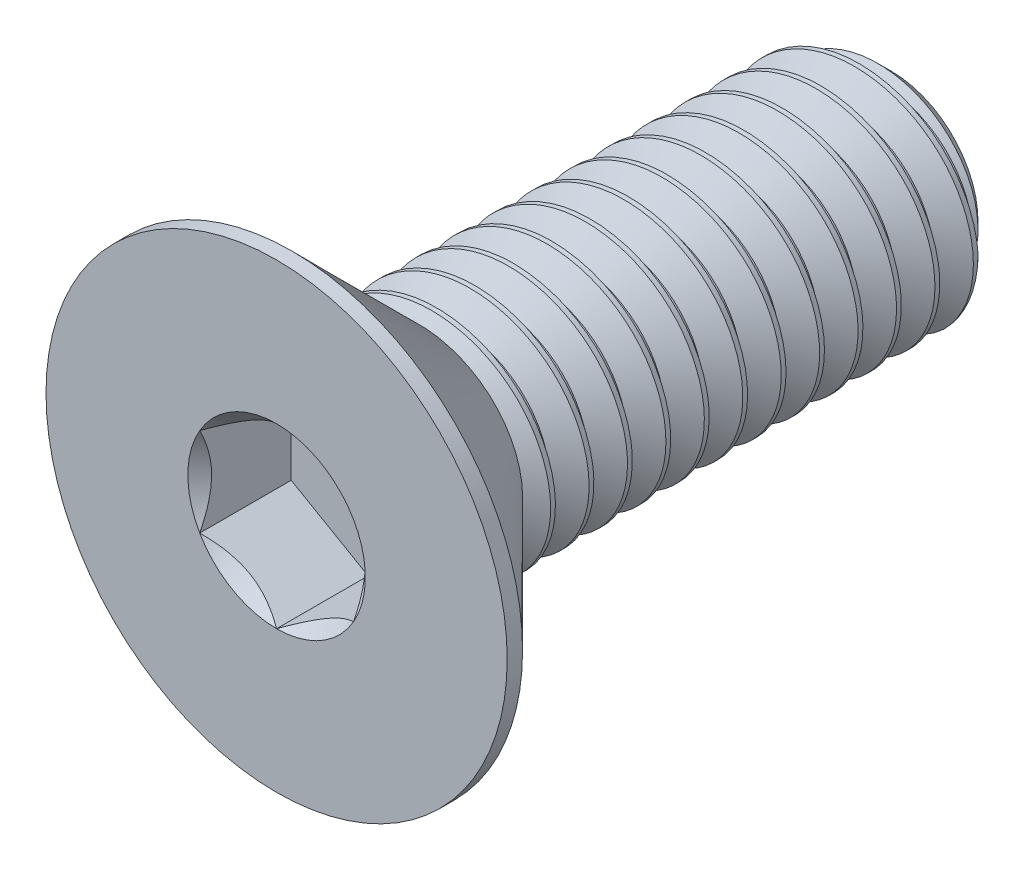
SolidWorks part; units mm, degrees
ref_plane "Front" through (0, 0, 0) normal (0, 0, 1) x (1, 0, 0)
ref_plane "Top" through (0, 0, 0) normal (0, 1, 0) x (1, 0, 0)
ref_plane "Right" through (0, 0, 0) normal (1, 0, 0) x (0, 0, -1)
sketch "Sketch1" plane through (0, 0, 0) normal (1, 0, 0) x (0, 0, -1)
  line L0 (0, 3) -> (0.2, 3) construction
  line L1 (0.2, 3) -> (1.7, 1.5) construction
  line L2 (0, 1.5) -> (8, 1.5)
  line L3 (8, 1.5) -> (8, 0)
  line L4 (8, 0) -> (0, 0)
  line L5 (0, 0) -> (0, 3) construction
  line L6 (0, 3) -> (0, -3) construction
  line L7 (8, 1.5) -> (8, -1.5) construction
  line L8 (0, -3) -> (0.2, -3) construction
  line L9 (0.2, -3) -> (1.7, -1.5) construction
  line L11 (0, 1.5) -> (0, 0)
  line L12 (1.7, 1.5) -> (1.7, 0) construction
  dimension "Head Ht" = 1.7
  dimension "Head Dia" = 6
  dimension "Dia" = 3
  dimension "Lg" = 8
  dimension "Head Angle" = 90
revolve "Revolve1" add sketch "Sketch1" angle 360 mid plane about L4
sketch "Sketch3" plane through (0, 0, -8) normal (0, 0, -1) x (-1, 0, 0)
  circle A0 centre (0, 0) radius 1.5
curve "Helix/Spiral1" pitch 0.5 height 8 radius 1.5 centre (0, 0, -8) axis (0, 0, 1) start towards (0, 1, 0)
sketch "Sketch2" plane through (0, 0, 0) normal (1, 0, 0) x (0, 0, -1)
  line L0 (8, 1.5) -> (8.4375, 1.5)
  line L1 (8.4375, 1.5) -> (8.25, 1.1752)
  line L2 (8.25, 1.1752) -> (8.1875, 1.1752)
  line L3 (8.1875, 1.1752) -> (8, 1.5)
  line L4 (8.0938, 1.3376) -> (8.3438, 1.3376) construction
  dimension "D1" = 60
  dimension "D2" = 0.0625
  dimension "D3" = 0.25
chamfer "Chamfer1" distance 0.375 angle 45 1 edges at (0, 1.5, -8)
sweep "Cut-Sweep1" cut profiles "Sketch2" path "Helix/Spiral1" align with end faces yes
sketch "Sketch7" plane through (0, 0, 0) normal (1, 0, 0) x (0, 0, -1)
  line L0 (0, 3) -> (0.2, 3) construction
  line L1 (0.2, 3) -> (1.7, 1.5) construction
  line L2 (0, 3) -> (0.2, 3)
  line L3 (0.2, 3) -> (1.7, 1.5)
  line L4 (1.7, 1.5) -> (1.7, 0) construction
  line L5 (1.7, 1.5) -> (1.7, 0)
  line L7 (0, 0) -> (0, 3) construction
  line L8 (0, 0) -> (0, 3)
  line L9 (0, 0) -> (1.7, 0)
  line L10 (3.3, 0) -> (-3.3, 0) construction
revolve "Revolve2" add sketch "Sketch7" angle 360 mid plane about L9
ref_plane "Plane1" through (0, 0, -1.7) normal (0, 0, 1) x (1, 0, 0)
sketch "Sketch8" plane through (0, 0, -1.7) normal (0, 0, 1) x (1, 0, 0)
  circle A0 centre (0, 0) radius 1.5
extrude "Boss-Extrude1" add sketch "Sketch8" against normal through all draft 45
sketch "Sketch5" plane through (0, 0, 0) normal (0, 0, 1) x (1, 0, 0)
  line L1 (1, -0.5774) -> (1, 0.5774)
  line L2 (1, 0.5774) -> (0, 1.1547)
  line L3 (0, 1.1547) -> (-1, 0.5774)
  line L4 (-1, 0.5774) -> (-1, -0.5774)
  line L5 (-1, -0.5774) -> (0, -1.1547)
  line L6 (0, -1.1547) -> (1, -0.5774)
  circle A0 centre (0, 0) radius 1 construction
  dimension "Hex" = 2
extrude "Cut-Extrude2" cut sketch "Sketch5" against normal blind 1.19
sketch "Sketch6" plane through (0, 0, 0) normal (0, 0, 1) x (1, 0, 0)
  circle A0 centre (0, 0) radius 1.1547
extrude "Cut-Extrude3" cut sketch "Sketch6" against normal blind 1.19 draft 45
sketch "Sketch9" [suppressed] plane through (0, 0, -1.5) normal (0, 0, 1) x (1, 0, 0)
  circle A1 centre (0, 0) radius 1.25
  circle A2 centre (0, 0) radius 1.25
  point P0 (0, 1.25)
  dimension "D1" = 0
extrude "Boss-Extrude2" [suppressed] add sketch "Sketch9" against normal offset from surface (3.5 mm away) 26 up to face at (0, 1.125, -8)
fillet "Fillet1" [suppressed] radius 0.3
sketch "Sketch10" plane through (0, 0, 0) normal (1, 0, 0) x (0, 0, -1)
  line L0 (8, 1.5) -> (8, -1.5) construction
  point P0 (7.25, -1.5)
  dimension "D1" = 0.75
equation "\"D3@Helix/Spiral1\" = \"Lg@Sketch1\""
equation "\"D2@Sketch2\" = \"D4@Helix/Spiral1\" * .125"
equation "\"D3@Sketch2\" = \"D4@Helix/Spiral1\" * .5"
equation "\"D1@Chamfer1\" = \"D4@Helix/Spiral1\" * .75"
equation "\"D1@Cut-Extrude2\" = \"Head Ht@Sketch1\" * .7"
equation "\"D1@Sketch10\" = \"D4@Helix/Spiral1\" * 1.5"
equation "\"D1@Cut-Extrude3\" = \"D1@Cut-Extrude2\""
equation "\"D1@Fillet1\" = \"Dia@Sketch1\" * .1"
